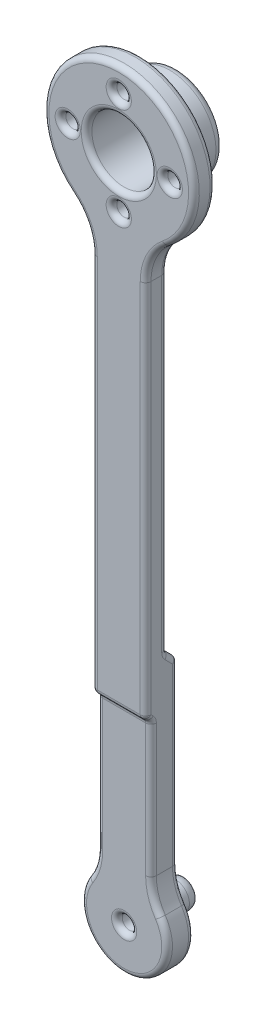
SolidWorks part; units mm, degrees
ref_plane "Front Plane" through (0, 0, 0) normal (0, 0, 1) x (1, 0, 0)
ref_plane "Top Plane" through (0, 0, 0) normal (0, 1, 0) x (1, 0, 0)
ref_plane "Right Plane" through (0, 0, 0) normal (1, 0, 0) x (0, 0, -1)
ref_plane "Plane1" through (0, 0, 7.5) normal (0, 0, -1) x (-1, 0, 0)
sketch "Sketch1" plane through (0, 0, 7.5) normal (0, 0, -1) x (-1, 0, 0)
  line L0 (-45, 171.9233) -> (-45, 66.245)
  line L1 (-35, 66.245) -> (-35, 171.9233)
  arc A0 (-35, 171.9233) -> (-45, 171.9233) centre (-40, 185) ccw
  arc A1 (-45, 66.245) -> (-35, 66.245) centre (-40, 60) ccw
extrude "Boss-Extrude1" add sketch "Sketch1" against normal blind 3
sketch "Sketch2" plane through (0, 0, 7.5) normal (0, 0, -1) x (-1, 0, 0)
  line L0 (-45, 66.245) -> (-45, 171.9233)
  line L1 (-45, 171.9233) -> (-35, 171.9233)
  line L2 (-35, 171.9233) -> (-35, 66.245)
  arc A0 (-35, 66.245) -> (-45, 66.245) centre (-40, 60) cw
extrude "Boss-Extrude2" add sketch "Sketch2" along normal blind 2
sketch "Sketch3" plane through (0, 171.9233, 0) normal (0, 1, 0) x (-1, 0, 0)
  line L0 (-35, 5.5) -> (-35, 7.5)
  line L1 (-35, 7.5) -> (-45, 7.5)
  line L2 (-45, 7.5) -> (-45, 5.5)
  line L3 (-45, 5.5) -> (-35, 5.5)
extrude "Cut-Extrude1" cut sketch "Sketch3" against normal blind 66.9233
sketch "Sketch4" plane through (0, 0, 10.5) normal (0, 0, 1) x (1, 0, 0)
  line L0 (35, 96) -> (35, 171.9233)
  line L1 (45, 171.9233) -> (45, 96)
  line L2 (45, 96) -> (35, 96)
  arc A0 (35, 171.9233) -> (45, 171.9233) centre (40, 185) cw
extrude "Boss-Extrude3" add sketch "Sketch4" along normal blind 1
sketch "Sketch5" plane through (0, 0, 7.5) normal (0, 0, -1) x (-1, 0, 0)
  circle A0 centre (-40, 185) radius 14
extrude "Boss-Extrude4" add sketch "Sketch5" along normal blind 2
sketch "Sketch6" plane through (0, 0, 5.5) normal (0, 0, -1) x (-1, 0, 0)
  circle A0 centre (-40, 185) radius 12.5
extrude "Boss-Extrude5" add sketch "Sketch6" along normal blind 4
draft "Draft1" type of draft neutral plane draft angle 45 faces to draft 1 face at (40, 96, 11) neutral plane through (40, 185, 11.5) neutral plane normal (0, 0, 1) parameters "D1"=45
draft "Draft2" type of draft neutral plane draft angle 45 faces to draft 1 face at (40, 105, 6.5) neutral plane through (40, 185, 7.5) neutral plane normal (0, 0, -1) parameters "D1"=45
ref_plane "Plane2" through (0, 60, 0) normal (0, -1, 0) x (1, 0, 0)
sketch "Sketch7" plane through (0, 60, 0) normal (0, -1, 0) x (1, 0, 0)
  line L0 (42, 5.5) -> (40, 5.5)
  line L1 (40, 5.5) -> (40, 5)
  line L2 (40, 5) -> (42, 5)
  line L3 (42, 5) -> (42, 5.5)
  line L4 (40, 5.5) -> (40, 5) construction
revolve "Revolve1" add sketch "Sketch7" angle 360 about L4 reverse direction yes
hole_wizard "HoleWzd1" positions "Sketch9" profile "Sketch8" hole size "Ø20.0" standard "ANSI Metric"
sketch "Sketch9" plane through (0, 0, 11.5) normal (0, 0, 1) x (1, 0, 0)
  point P0 (40, 185)
sketch "Sketch8" plane through (40, 185, 11.5) normal (1, 0, 0) x (0, -1, 0)
  line L0 (0, 0) -> (0, 10)
  line L1 (0, 10) -> (10, 10)
  line L2 (10, 10) -> (10, 0)
  line L5 (10, 0) -> (0, 0)
  line L11 (0, -6.35) -> (0, 107.95) construction
  dimension "Thru Hole Dia." = 20
  dimension "Thru Hole Depth" = 10
hole_wizard "HoleWzd2" positions "Sketch11" profile "Sketch10" hole size "Ø3.0" standard "ANSI Metric"
sketch "Sketch11" plane through (0, 0, 5) normal (0, 0, -1) x (-1, 0, 0)
  point P0 (-40, 60)
sketch "Sketch10" plane through (40, 60, 5) normal (1, 0, 0) x (0, 1, 0)
  line L0 (0, 0) -> (0, 6.5)
  line L1 (0, 6.5) -> (1.5, 6.5)
  line L2 (1.5, 6.5) -> (1.5, 0)
  line L5 (1.5, 0) -> (0, 0)
  line L11 (0, -6.35) -> (0, 107.95) construction
  dimension "Thru Hole Dia." = 3
  dimension "Thru Hole Depth" = 6.5
fillet "Fillet1" radius 10 4 edges at (35, 171.9233, 9.5) (45, 171.9233, 9.5) (45, 66.245, 8) (35, 66.245, 8) tangent propagation no
sketch "Sketch12" plane through (0, 0, 10.5) normal (0, 0, 1) x (1, 0, 0)
  circle A0 centre (40, 60) radius 2.65
  circle A2 centre (40, 60) radius 1.5 construction
  dimension "D1" = 5.3
extrude "Boss-Extrude6" add sketch "Sketch12" against normal offset from surface (11 mm away) 6 up to face at (38, 60, 5.5) offset beyond the face yes
sketch "Sketch13" plane through (0, 0, 1.5) normal (0, 0, -1) x (-1, 0, 0)
  circle A0 centre (-40, 185) radius 12.5 construction
  circle A1 centre (-40, 185) radius 12.5
extrude "Cut-Extrude2" cut sketch "Sketch13" against normal up to surface (4 mm away) up to face at (27.5, 185, 5.5)
sketch "Sketch14" plane through (0, 0, 5.5) normal (0, 0, -1) x (-1, 0, 0)
  circle A0 centre (-40, 185) radius 14 construction
  circle A1 centre (-40, 185) radius 14
extrude "Boss-Extrude7" add sketch "Sketch14" against normal up to surface (6 mm away) up to face at (50, 185, 11.5)
sketch "Sketch15" plane through (0, 0, 5.5) normal (0, 0, -1) x (-1, 0, 0)
  circle A0 centre (-40, 185) radius 8.6
  circle A1 centre (-40, 185) radius 14 construction
  dimension "D1" = 17.2
extrude "Boss-Extrude8" add sketch "Sketch15" along normal blind 5
fillet "Fillet2" radius 1.5 1 edges at (31.4, 185, 0.5)
sketch "Sketch16" plane through (0, 0, 5.5) normal (0, 0, -1) x (-1, 0, 0)
  circle A1 centre (-40, 185) radius 14 construction
  circle A2 centre (-40, 185) radius 10.1
  circle A3 centre (-40, 185) radius 10.1
  circle A4 centre (-40, 185) radius 14
  dimension "D1" = 1.5
extrude "Cut-Extrude3" cut sketch "Sketch16" against normal blind 2
sketch "Sketch18" plane through (0, 0, 0.5) normal (0, 0, -1) x (-1, 0, 0)
  circle A0 centre (-40, 185) radius 6
  circle A1 centre (-40, 185) radius 7.1 construction
  dimension "D1" = 12
extrude "Cut-Extrude4" cut sketch "Sketch18" against normal through all
sketch "Sketch19" plane through (0, 0, 11.5) normal (0, 0, 1) x (1, 0, 0)
  line L0 (40, 194.5) -> (40, 185) construction
  line L1 (40, 185) -> (40, 175.5) construction
  line L2 (30.5, 185) -> (40, 185) construction
  line L3 (40, 185) -> (49.5, 185) construction
  circle A0 centre (40, 194.5) radius 1.35
  circle A1 centre (49.5, 185) radius 1.35
  circle A2 centre (30.5, 185) radius 1.35
  circle A3 centre (40, 175.5) radius 1.35
  circle A4 centre (40, 185) radius 6 construction
  dimension "D2" = 2.7
  dimension "D1" = 9.5
extrude "Cut-Extrude5" cut sketch "Sketch19" against normal blind 3
fillet "Fillet3" radius 1.5 1 edges at (42.65, 60, -0.5) second distance 0.5 first distance on face at (42.65, 60, -0.5)
sketch "Sketch21" plane through (0, 0, -0.5) normal (0, 0, -1) x (-1, 0, 0)
  circle A0 centre (-40, 60) radius 1.35
  circle A1 centre (-40, 60) radius 2.65 construction
  dimension "D1" = 2.7
extrude "Cut-Extrude8" cut sketch "Sketch21" against normal through all contours A0
fillet "Fillet5" radius 1 1 edges at (38.65, 60, 10.5)
sketch "Sketch22" plane through (0, 0, 5.5) normal (0, 0, -1) x (-1, 0, 0)
  circle A1 centre (-40, 60) radius 3.45
  circle A2 centre (-40, 60) radius 2.65 construction
  circle A3 centre (-40, 60) radius 1.35 construction
  circle A4 centre (-40, 60) radius 1.35
  dimension "D1" = 0.8
extrude "Boss-Extrude9" add sketch "Sketch22" along normal blind 1.3
fillet "Fillet6" radius 1 35 edges at (45, 95.5, 11) (35, 95.5, 11) (35, 104, 6.5) (45, 104, 6.5) (35, 86.4749, 5.5) (34.5743, 67.0631, 5.5) (40, 52, 5.5) (45.4257, 67.0631, 5.5) (45, 86.4749, 5.5) (40, 103, 5.5) (45, 131.1325, 11.5) (40, 96, 11.5) (35, 131.1325, 11.5) (34.0139, 170.5951, 11.5) (40, 199, 11.5) (45.9861, 170.5951, 11.5) (34, 185, 11.5) (41.35, 175.5, 11.5) (31.85, 185, 11.5) (50.85, 185, 11.5) (41.35, 194.5, 11.5) (45, 82.4749, 10.5) (45.4257, 67.0631, 10.5) (40, 52, 10.5) (34.5743, 67.0631, 10.5) (35, 82.4749, 10.5) (40, 95, 10.5) (29.9, 185, 7.5) (40, 105, 7.5) (45, 135.6325, 7.5) (45.9861, 170.5951, 7.5) (40, 199, 7.5) (34.0139, 170.5951, 7.5) (35, 135.6325, 7.5) (43.45, 60, 5.5)
